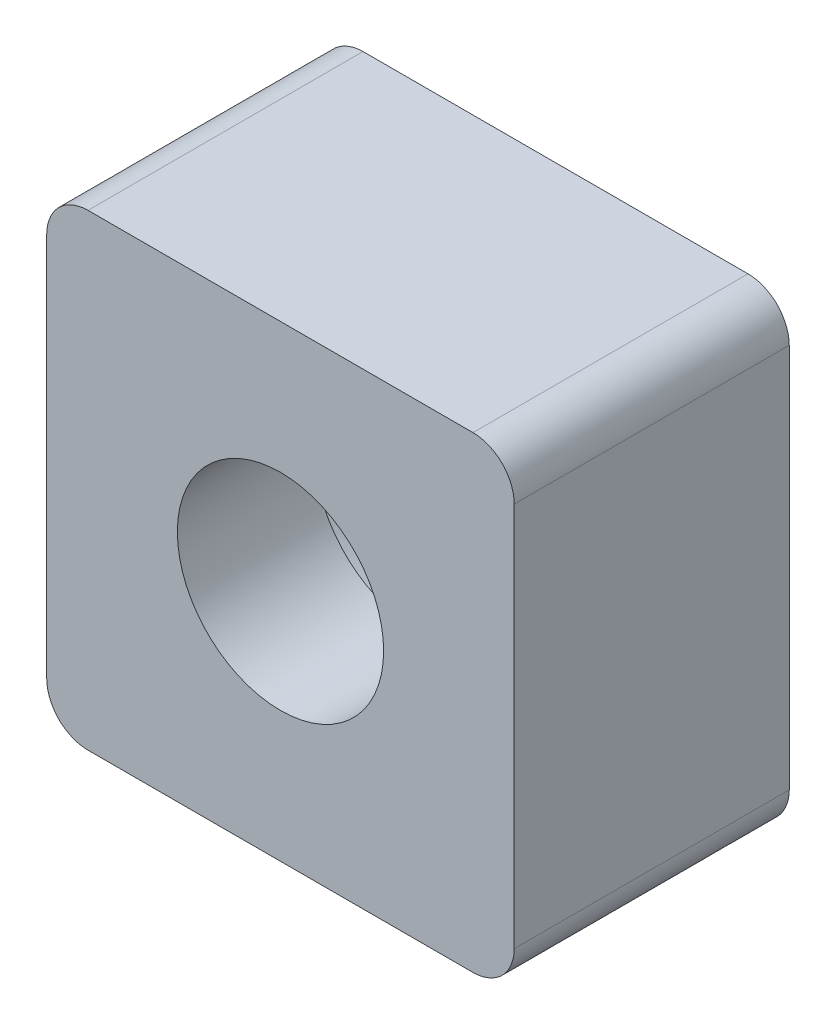
SolidWorks part; units mm, degrees
ref_plane "Front" through (0, 0, 0) normal (0, 0, 1) x (1, 0, 0)
ref_plane "Top" through (0, 0, 0) normal (0, 1, 0) x (1, 0, 0)
ref_plane "Right" through (0, 0, 0) normal (1, 0, 0) x (0, 0, -1)
sketch "Sketch1" plane through (0, 0, 0) normal (0, 0, 1) x (1, 0, 0)
  line L0 (-3.3999, 2.8) -> (-3.3999, -2.8)
  line L1 (-2.7999, -3.4) -> (2.7999, -3.4)
  line L2 (3.3999, -2.8) -> (3.3999, 2.8)
  line L3 (2.7999, 3.4) -> (-2.7999, 3.4)
  spline S0 degree 3 poles (-3.3999, -2.8) (-3.3999, -2.9531) (-3.2719, -3.272) (-2.953, -3.4) (-2.7999, -3.4) knots -1.570796 -1.570796 -1.570796 -1.570796 -0.785398 0 0 0 0
  spline S1 degree 3 poles (2.7999, -3.4) (2.953, -3.4) (3.2719, -3.272) (3.3999, -2.9531) (3.3999, -2.8) knots 0 0 0 0 0.785398 1.570796 1.570796 1.570796 1.570796
  spline S2 degree 3 poles (3.3999, 2.8) (3.3999, 2.9531) (3.2719, 3.272) (2.953, 3.4) (2.7999, 3.4) knots 1.570796 1.570796 1.570796 1.570796 2.356194 3.141593 3.141593 3.141593 3.141593
  spline S3 degree 3 poles (-2.7999, 3.4) (-2.953, 3.4) (-3.2719, 3.272) (-3.3999, 2.9531) (-3.3999, 2.8) knots -3.141593 -3.141593 -3.141593 -3.141593 -2.356194 -1.570796 -1.570796 -1.570796 -1.570796
extrude "Boss-Extrude1" add sketch "Sketch1" along normal blind 4
sketch "Sketch2" plane through (0, 0, 4) normal (0, 0, 1) x (1, 0, 0)
  line L0 (0, 3.4) -> (0, -3.4) construction
  line L1 (2.7999, 3.4) -> (-2.7999, 3.4) construction
  line L2 (-2.7999, -3.4) -> (2.7999, -3.4) construction
  line L3 (-3.3999, 0) -> (3.3999, 0) construction
  line L4 (-3.3999, 2.8) -> (-3.3999, -2.8) construction
  line L5 (3.3999, -2.8) -> (3.3999, 2.8) construction
  circle A0 centre (0, 0) radius 1.5
  dimension "D1" = 3
extrude "Cut-Extrude1" cut sketch "Sketch2" against normal up to surface (4 mm away) up to face at (0, 0, 0)
sketch "Sketch3" plane through (0, 0, 0) normal (0, 0, -1) x (-1, 0, 0)
  line L0 (0, 3.4) -> (0, -3.4) construction
  line L1 (-2.7999, 3.4) -> (2.7999, 3.4) construction
  line L2 (2.7999, -3.4) -> (-2.7999, -3.4) construction
  line L3 (-3.3999, 0) -> (3.3999, 0) construction
  line L4 (-3.3999, -2.8) -> (-3.3999, 2.8) construction
  line L5 (3.3999, 2.8) -> (3.3999, -2.8) construction
  circle A0 centre (0, 0) radius 3
extrude "Cut-Extrude2" cut sketch "Sketch3" against normal blind 2
